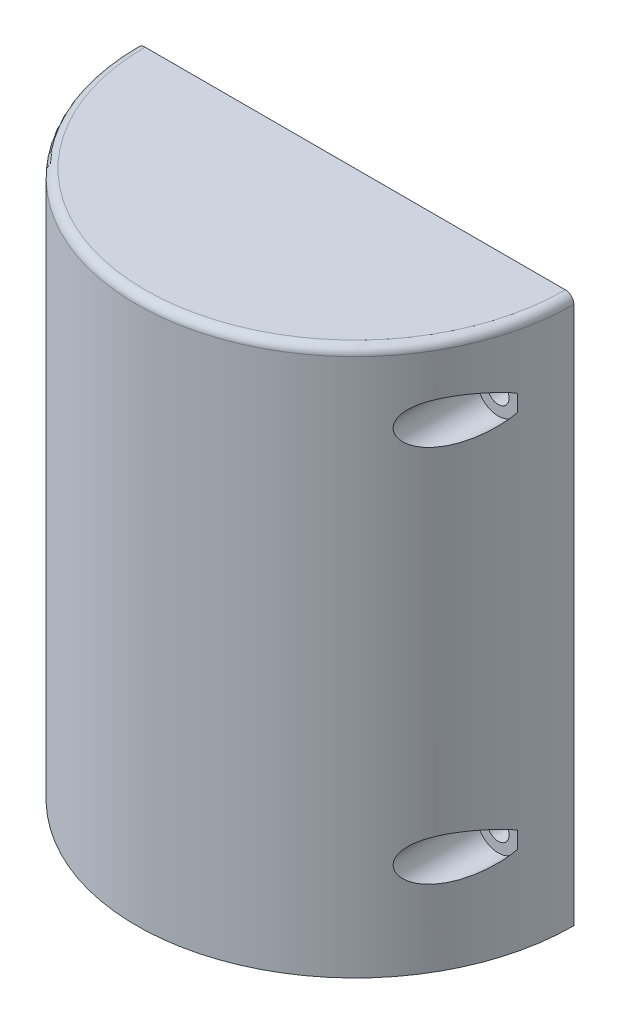
SolidWorks part; units mm, degrees
material "ABS"
ref_plane "Спереди" through (0, 0, 0) normal (0, 0, 1) x (1, 0, 0)
ref_plane "Сверху" through (0, 0, 0) normal (0, 1, 0) x (1, 0, 0)
ref_plane "Справа" through (0, 0, 0) normal (1, 0, 0) x (0, 0, -1)
sketch "Эскиз1" plane through (0, 0, 0) normal (0, 1, 0) x (1, 0, 0)
  line L0 (-26, 0) -> (-23, 0)
  line L1 (23, 0) -> (26, 0)
  arc A2 (26, 0) -> (-26, 0) centre (0, 0) cw
  arc A3 (23, 0) -> (-23, 0) centre (0, 0) cw
  dimension "D1" = 23
  dimension "D2" = 26
extrude "Бобышка-Вытянуть1" add sketch "Эскиз1" along normal blind 65
sketch "Эскиз2" plane through (0, 65, 0) normal (0, 1, 0) x (1, 0, 0)
  line L0 (-26, 0) -> (26, 0)
  arc A3 (26, 0) -> (-26, 0) centre (0, 0) cw
  arc A4 (-26, 0) -> (26, 0) centre (0, 0) ccw construction
sketch "Эскиз12" plane through (0, 0, 0) normal (0, 0, -1) x (-1, 0, 0)
  line L0 (23, 65) -> (23, 0) construction
  line L2 (23, 11.5) -> (23, 56.5) construction
  line L4 (23, 11.5) -> (23, 56.5) construction
  line L5 (23, 65) -> (23, 0) construction
  line L6 (0, 59.3805) -> (0, 0) construction
  line L7 (-23, 0) -> (23, 0) construction
  line L8 (23, 65) -> (23, 0) construction
  circle A1 centre (23, 56.5) radius 3
  circle A3 centre (23, 11.5) radius 3
  circle A4 centre (-23, 56.5) radius 3
  circle A5 centre (-23, 11.5) radius 3
  point P8 (23, 34)
  dimension "D3" = 6
  dimension "D1" = 45
  dimension "D2" = 34
extrude "Бобышка-Вытянуть5" add sketch "Эскиз12" against normal up to surface (12.6095 mm away) up to face at (0, 32.5, 11.5)
sketch "Эскиз16" plane through (0, 0, 0) normal (0, 0, -1) x (-1, 0, 0)
  line L0 (0, 60.4355) -> (0, 0) construction
  circle A1 centre (23, 56.5) radius 1.3
  circle A3 centre (23, 11.5) radius 1.3
  circle A4 centre (-23, 11.5) radius 1.3
  circle A5 centre (-23, 56.5) radius 1.3
  circle A6 centre (-23, 56.5) radius 2.5
  circle A7 centre (-23, 11.5) radius 2.5
  circle A8 centre (23, 11.5) radius 2.5
  circle A9 centre (23, 56.5) radius 2.5
  dimension "D1" = 2.6
  dimension "D2" = 5
extrude "Вырез-Вытянуть2" cut sketch "Эскиз16" against normal through all contours A1 | A3 | A4 | A5
extrude "Бобышка-Вытянуть6" add sketch "Эскиз2" against normal blind 3
fillet "Скругление1" radius 1 1 edges at (0, 65, 26)
extrude "Вырез-Вытянуть4" cut sketch "Эскиз16<4>" against normal through all from offset 6 contours A9 | A7 | A6 | A8 offset against normal yes
sketch "Эскиз16<4>" plane through (0, 0, 0) normal (0, 0, -1) x (-1, 0, 0) same geometry as "Эскиз16"
ref_plane "Плоскость1" through (-22.5167, 0, 13) normal (-0.866, 0, 0.5) x (0, -1, 0)
sketch "Эскиз20" plane through (-26, 0, 6.9667) normal (0.866, 0, -0.5) x (-0.5, 0, -0.866)
  line L0 (6.0333, 64) -> (6.0333, 0) construction
  line L1 (-10.4667, 48.9) -> (2.0333, 48.9)
  line L2 (-10.4667, 48.9) -> (-10.4667, 18)
  line L3 (-10.4667, 18) -> (2.0333, 18)
  line L4 (2.0333, 48.9) -> (2.0333, 18)
  dimension "D1" = 30.9
  dimension "D2" = 12.5
  dimension "D3" = 18
  dimension "D4" = 4
extrude "Вырез-Вытянуть6" cut sketch "Эскиз20" along normal blind 2
sketch "Эскиз21" plane through (-20.7846, 0, 12) normal (-0.866, 0, 0.5) x (0.5, 0, 0.866)
  line L0 (-6.75, 41.03) -> (-6.75, 25.87)
  line L1 (-6.75, 25.87) -> (1.25, 23.7264)
  line L2 (1.25, 23.7264) -> (1.25, 43.1736)
  line L3 (1.25, 43.1736) -> (-6.75, 41.03)
  line L4 (-9, 48.9) -> (-9, 18) construction
  line L7 (-9, 48.9) -> (3.5, 48.9) construction
  point P2 (-2.75, 48.9)
  point P7 (-2.75, 42.1018)
  point P10 (1.25, 33.45)
  point P11 (-6.75, 33.45)
  point P12 (-9, 33.45)
  dimension "D1" = 15.16
  dimension "D2" = 30
  dimension "D3" = 8
extrude "Вырез-Вытянуть7" cut sketch "Эскиз21" against normal up to next
hole_wizard "Сверло под метчик  спиральное M31" positions "Эскиз22" profile "Эскиз23" hole size "M3x0.5" standard "Ansi Metric" end condition up to next
sketch "Эскиз22" plane through (-20.7846, 0, 12) normal (-0.866, 0, 0.5) x (0.5, 0, 0.866)
  line L0 (1.25, 23.7264) -> (1.25, 43.1736) construction
  line L1 (3.5, 18) -> (-9, 18) construction
  point P0 (-2.75, 45.95)
  point P2 (-2.75, 20.95)
  point P8 (1.25, 33.45)
  point P12 (-2.75, 18)
  dimension "D1" = 25
  dimension "D2" = 12.5
sketch "Эскиз23" plane through (-22.1596, 45.95, 9.6184) normal (0, 1, 0) x (0.5, 0, 0.866)
  line L0 (0, 0) -> (0, 1.165)
  line L1 (0, 1.165) -> (1.575, 1.165)
  line L2 (1.575, 1.165) -> (1.575, 0)
  line L5 (1.575, 0) -> (0, 0)
  line L11 (0, -6.35) -> (0, 107.95) construction
  dimension "Диаметр сквозного отверстия" = 3.15
  dimension "Глубина сквозного отверстия" = 1.165
fillet "Скругление3" radius 1.5 8 edges at (-25.4546, 18, 4.3039) (-19.7982, 18, 15.4719) (-25.4546, 48.9, 4.3039) (-19.7982, 48.9, 15.4719) (-23.288, 41.03, 5.6511) (-19.7119, 43.1736, 12.824) (-23.288, 25.87, 5.6511) (-19.7119, 23.7264, 12.824)
fillet "Скругление2" radius 0.75 8 edges at (-24.1596, 33.45, 6.1543) (-22.3537, 41.9978, 9.2822) (-20.1596, 33.45, 13.0825) (-22.3537, 24.9022, 9.2822) (-24.0046, 26.1078, 6.4228) (-24.0046, 40.7922, 6.4228) (-20.453, 42.4088, 12.5743) (-20.453, 24.4912, 12.5743)
